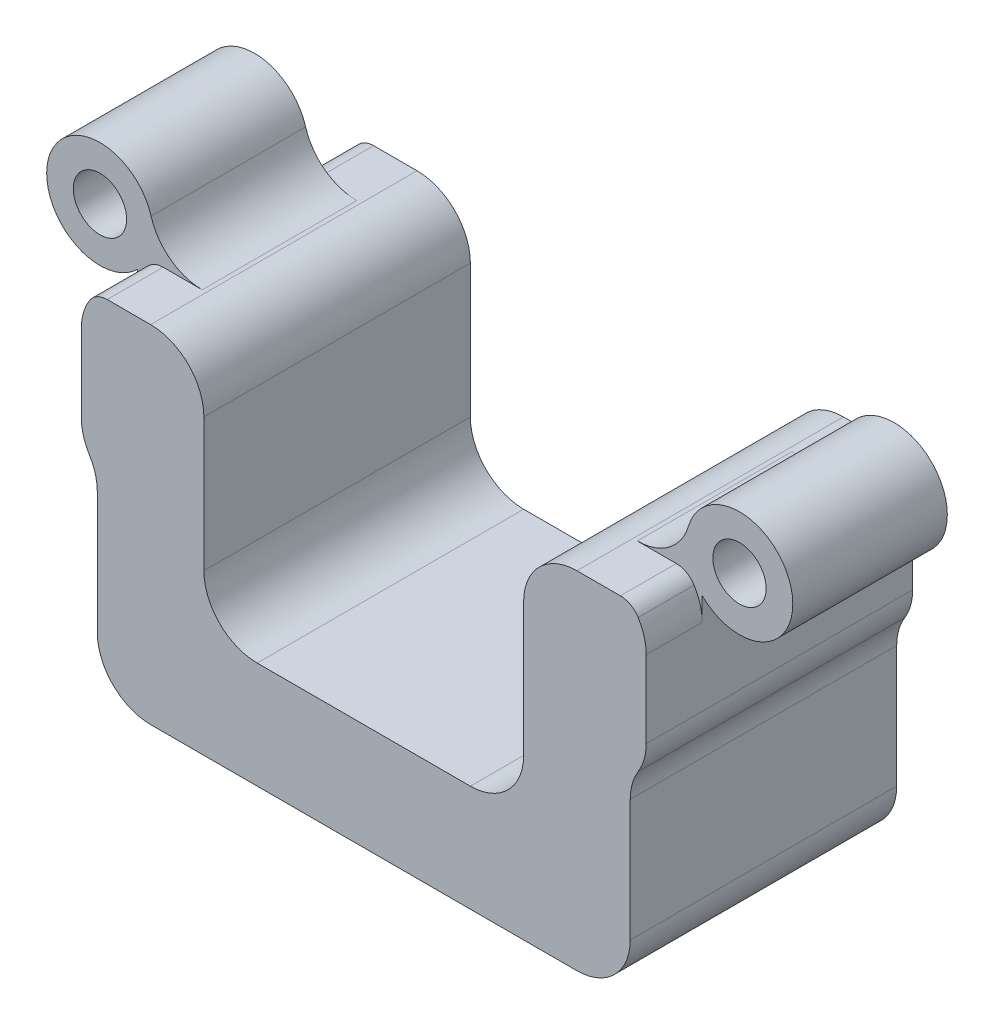
SolidWorks part; units mm, degrees
ref_plane "Front Plane" through (0, 0, 0) normal (0, 0, 1) x (1, 0, 0)
ref_plane "Top Plane" through (0, 0, 0) normal (0, 1, 0) x (1, 0, 0)
ref_plane "Right Plane" through (0, 0, 0) normal (1, 0, 0) x (0, 0, -1)
sketch "Sketch1" plane through (0, 0, 0) normal (0, 0, 1) x (1, 0, 0)
  line L0 (-5.08, -5.08) -> (-5.08, 11.43)
  line L1 (0, 0) -> (15.24, 0)
  line L2 (0, 0) -> (0, 11.43)
  line L4 (15.24, 0) -> (15.24, 11.43)
  line L6 (20.32, -5.08) -> (20.32, 11.43)
  line L7 (-5.08, -5.08) -> (20.32, -5.08)
  line L8 (-5.08, 11.43) -> (0, 11.43)
  line L9 (-5.08, -5.08) -> (-5.08, 22.86) construction
  line L10 (0, 0) -> (0, 17.78) construction
  line L11 (15.24, 0) -> (15.24, 17.78) construction
  line L12 (20.32, -5.08) -> (20.32, 22.86) construction
  line L13 (-5.08, 22.86) -> (20.32, 22.86) construction
  line L14 (0, 17.78) -> (15.24, 17.78) construction
  line L15 (15.24, 11.43) -> (20.32, 11.43)
  dimension "D1" = 15.24
  dimension "D2" = 16.51
  dimension "D3" = 5.08
extrude "Boss-Extrude1" add sketch "Sketch1" along normal blind 12.7
sketch "Sketch3" plane through (0, 0, 12.7) normal (0, 0, 1) x (1, 0, 0)
  line L0 (-5.08, 5.08) -> (-5.08, 12.533)
  line L1 (-5.08, 11.43) -> (-5.08, -5.08) construction
  line L2 (-5.08, 12.533) -> (-7.62, 12.533)
  line L3 (-5.08, 5.08) -> (-5.842, 5.08)
  line L4 (-5.842, 5.08) -> (-5.842, 10.7191)
  arc A0 (-5.08, 12.533) -> (-5.842, 10.7191) centre (-7.62, 12.533) ccw
  circle A1 centre (-7.62, 12.533) radius 1.27
  dimension "D1" = 5.08
  dimension "D2" = 2.54
  dimension "D3" = 10.16
  dimension "D4" = 0.762
  dimension "D5" = 5.6391
extrude "Boss-Extrude2" add sketch "Sketch3" against normal blind 12.7
ref_plane "Plane1" through (7.62, 0, 0) normal (1, 0, 0) x (0, 0, -1)
ref_plane "Plane2" through (0, 0, 10.033) normal (0, 0, 1) x (1, 0, 0)
ref_plane "Plane3" through (0, 0, 6.35) normal (0, 0, 1) x (1, 0, 0)
sketch "Sketch9" plane through (0, 0, 10.033) normal (0, 0, 1) x (1, 0, 0)
  line L0 (-5.08, 12.533) -> (-5.08, 11.43) construction
  line L1 (-5.08, 12.533) -> (-5.08, 11.43)
  line L2 (-5.842, 10.7191) -> (-5.08, 11.43)
  line L3 (7.62, -6.2865) -> (7.62, 6.2865) construction
  line L4 (21.082, 10.7191) -> (20.32, 11.43)
  line L5 (20.32, 12.533) -> (20.32, 11.43)
  arc A4 (-5.08, 12.533) -> (-5.842, 10.7191) centre (-7.62, 12.533) ccw construction
  arc A5 (-5.08, 12.533) -> (-5.842, 10.7191) centre (-7.62, 12.533) ccw
  arc A6 (20.32, 12.533) -> (21.082, 10.7191) centre (22.86, 12.533) cw
extrude "Cut-Extrude6" cut sketch "Sketch9" along normal blind 13.462
fillet "Fillet2" radius 2.54 2 edges at (0, 11.43, 6.35) (15.24, 11.43, 6.35)
fillet "Fillet3" radius 2.54 2 edges at (15.24, 0, 6.35) (0, 0, 6.35)
mirror "Mirror1" about plane through (7.62, 0, 0) normal (1, 0, 0) of "Cut-Extrude6", "Boss-Extrude2"
mirror "Mirror3" about plane through (0, 0, 6.35) normal (0, 0, 1) of "Cut-Extrude6"
fillet "Fillet4" radius 2.54 8 edges at (20.32, 11.43, 6.35) (-5.08, 11.43, 6.35) (-5.842, 10.7191, 11.3665) (-5.842, 10.7191, 1.3335) (21.082, 10.7191, 1.3335) (21.082, 10.7191, 11.3665) (20.32, 5.08, 6.35) (-5.08, 5.08, 6.35)
fillet "Fillet5" radius 2.54 4 edges at (-5.842, 5.08, 6.35) (21.082, 5.08, 6.35) (20.32, -5.08, 6.35) (-5.08, -5.08, 6.35)
fillet "Fillet6" radius 1 4 edges at (-5.08, 11.43, 1.3335) (-5.08, 11.43, 11.3665) (20.32, 11.43, 11.3665) (20.32, 11.43, 1.3335)
